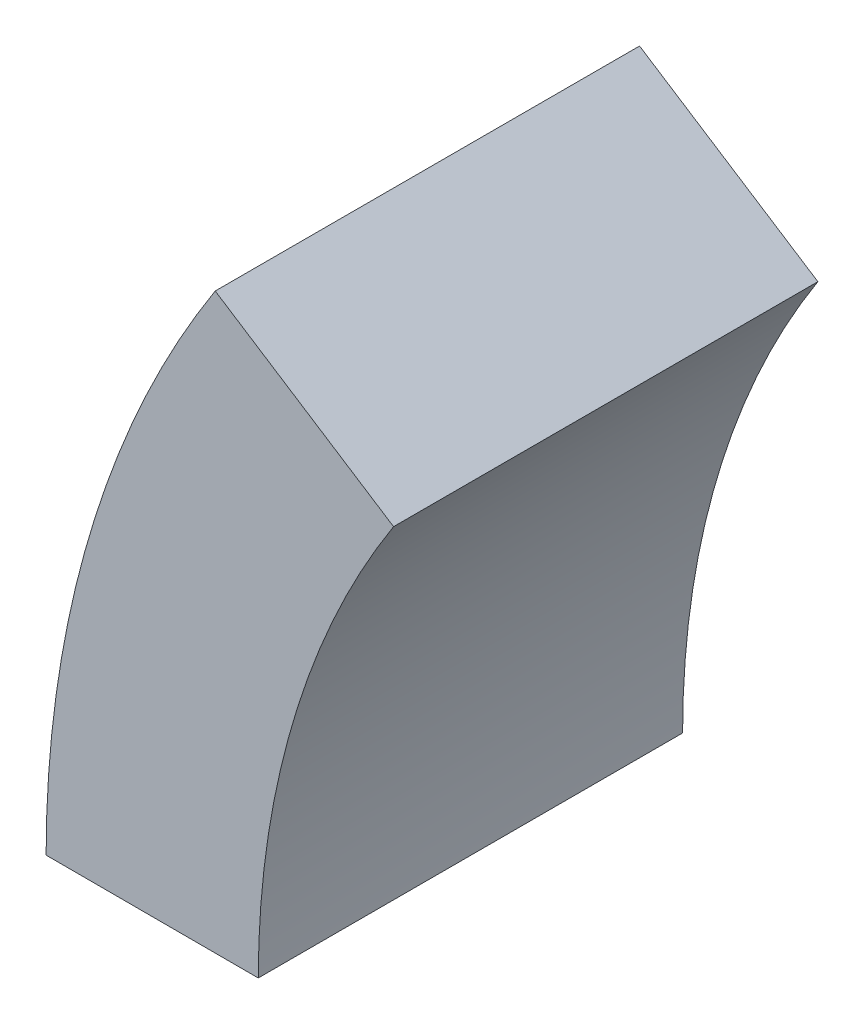
SolidWorks part; units mm, degrees
ref_plane "Front Plane" through (0, 0, 0) normal (0, 0, 1) x (1, 0, 0)
ref_plane "Top Plane" through (0, 0, 0) normal (0, 1, 0) x (1, 0, 0)
ref_plane "Right Plane" through (0, 0, 0) normal (1, 0, 0) x (0, 0, -1)
sketch "Sketch1" plane through (0, 0, 0) normal (0, 0, 1) x (1, 0, 0)
  circle A0 centre (0, 0) radius 63.5
  circle A1 centre (0, 0) radius 50.8
  dimension "D1" = 127
  dimension "D2" = 101.6
extrude "Boss-Extrude1" add sketch "Sketch1" along normal blind 25.4
sketch "Sketch2" plane through (0, 0, 0) normal (0, 1, 0) x (1, 0, 0)
  line L0 (-63.5, 0) -> (-63.5, -25.4) construction
  line L1 (-86.1901, -30.0161) -> (-40.8099, -30.0161)
  line L2 (-86.1901, -30.0161) -> (-86.1901, 4.6161)
  line L3 (-86.1901, 4.6161) -> (-40.8099, 4.6161)
  line L4 (-40.8099, -30.0161) -> (-40.8099, 4.6161)
  line L5 (-86.1901, -30.0161) -> (-40.8099, 4.6161) construction
  line L6 (-86.1901, 4.6161) -> (-40.8099, -30.0161) construction
  point P0 (-63.5, -12.7)
revolve "Cut-Revolve1" cut sketch "Sketch2" angle 0.08 about axis through (0, 0, 25.4) along (0, 0, -1)
revolve "Cut-Revolve2" cut sketch "Sketch2<2>" angle 327.2 about axis through (0, 0, 25.4) along (0, 0, -1) reverse direction yes
sketch "Sketch2<2>" plane through (0, 0, 0) normal (0, 1, 0) x (1, 0, 0) same geometry as "Sketch2"
